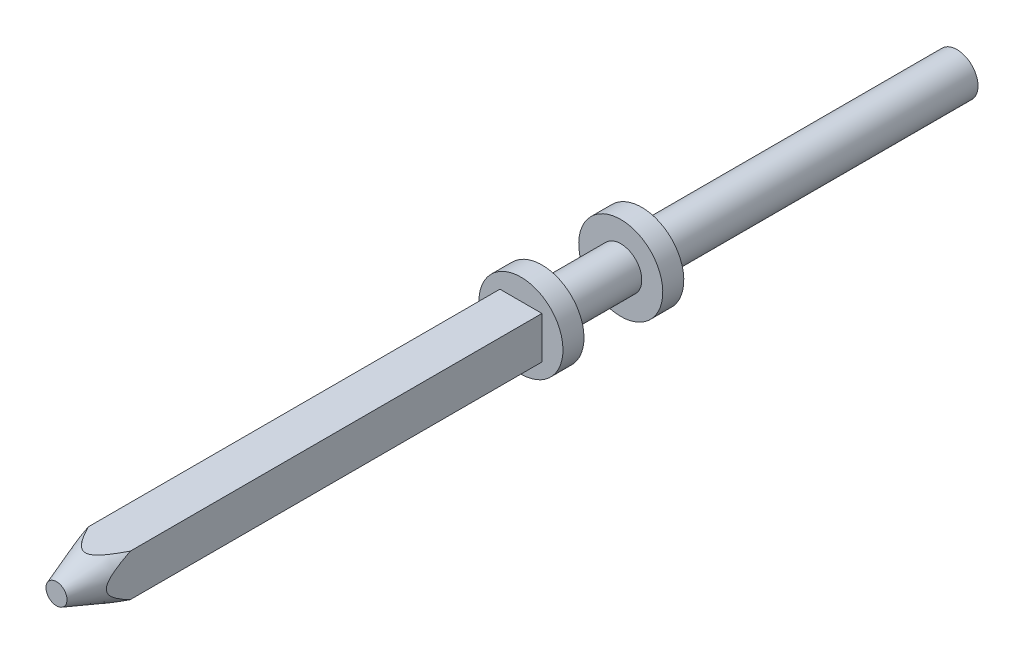
SolidWorks part; units mm, degrees
ref_plane "Plan de face" through (0, 0, 0) normal (0, 0, 1) x (1, 0, 0)
ref_plane "Plan de dessus" through (0, 0, 0) normal (0, 1, 0) x (1, 0, 0)
ref_plane "Plan de droite" through (0, 0, 0) normal (1, 0, 0) x (0, 0, -1)
sketch "Esquisse1" plane through (0, 0, 0) normal (0, 0, 1) x (1, 0, 0)
  line L1 (0, 0) -> (40, 0)
  line L2 (0, 0) -> (0, 40)
  line L3 (0, 40) -> (40, 40)
  line L4 (40, 0) -> (40, 40)
  dimension "D1" = 40
extrude "Boss.-Extru.1" add sketch "Esquisse1" along normal blind 392
sketch "Esquisse2" plane through (0, 0, 392) normal (0, 0, 1) x (1, 0, 0)
  line L0 (0, 0) -> (40, 40) construction
  circle A0 centre (20, 20) radius 10
  point P5 (20, 20)
  dimension "D1" = 20
extrude "Boss.-Extru.2" add sketch "Esquisse2" against normal blind 50 draft 20 from offset 50 draft outward yes
sketch "Esquisse3" plane through (0, 0, 392) normal (0, 0, -1) x (-1, 0, 0)
  line L1 (-40, 40) -> (0, 40)
  line L2 (-40, 40) -> (-40, 0)
  line L3 (-40, 0) -> (0, 0)
  line L4 (0, 40) -> (0, 0)
  arc A0 (-0.1215, 40) -> (-39.8785, 40) centre (-20, 20) ccw construction
  arc A1 (-0.1215, 40) -> (-39.8785, 40) centre (-20, 20) ccw
  arc A2 (-40, 39.8785) -> (-40, 0.1215) centre (-20, 20) ccw construction
  arc A3 (0, 0.1215) -> (0, 39.8785) centre (-20, 20) ccw construction
  arc A4 (-39.8785, 0) -> (-0.1215, 0) centre (-20, 20) ccw construction
  arc A5 (-40, 39.8785) -> (-40, 0.1215) centre (-20, 20) ccw
  arc A6 (0, 0.1215) -> (0, 39.8785) centre (-20, 20) ccw
  arc A7 (-39.8785, 0) -> (-0.1215, 0) centre (-20, 20) ccw
  arc M1 (-40, 39.8785) -> (-40, 0.1215) centre (-20, 20) ccw
  line M2 (-40, 0.1215) -> (-40, 39.8785)
extrude "Enlèv. mat.-Extru.1" cut sketch "Esquisse3" against normal through all contours L4 A6 | L1 A1 | M2 M1 | L3 A7 region at (20, 43.324, 392) region at (43.324, 20, 392) region at (-3.324, 20, 392) region at (20, -3.324, 392)
ref_plane "Plan1" through (20, 0, 0) normal (-1, 0, 0) x (0, 0, 1)
sketch "Esquisse5" plane through (20, 0, 0) normal (1, 0, 0) x (0, 0, -1)
  line L0 (0, 20) -> (415, 20) construction
  line L1 (0, 0) -> (0, 40) construction
  line L2 (0, 40) -> (0, 60)
  line L3 (0, 60) -> (20, 60)
  line L4 (20, 60) -> (20, 40)
  line L5 (20, 40) -> (95, 40)
  line L6 (415, 40) -> (415, 20)
  line L7 (0, 20) -> (0, 40)
  line L8 (415, 20) -> (0, 20)
  line L9 (115, 40) -> (415, 40)
  line L11 (95, 40) -> (95, 60)
  line L12 (95, 60) -> (115, 60)
  line L13 (115, 40) -> (115, 60)
  dimension "D1" = 320
  dimension "D2" = 40
  dimension "D3" = 20
  dimension "D4" = 80
  dimension "D5" = 115
revolve "Révolution1" add sketch "Esquisse5" angle 360 about L0
